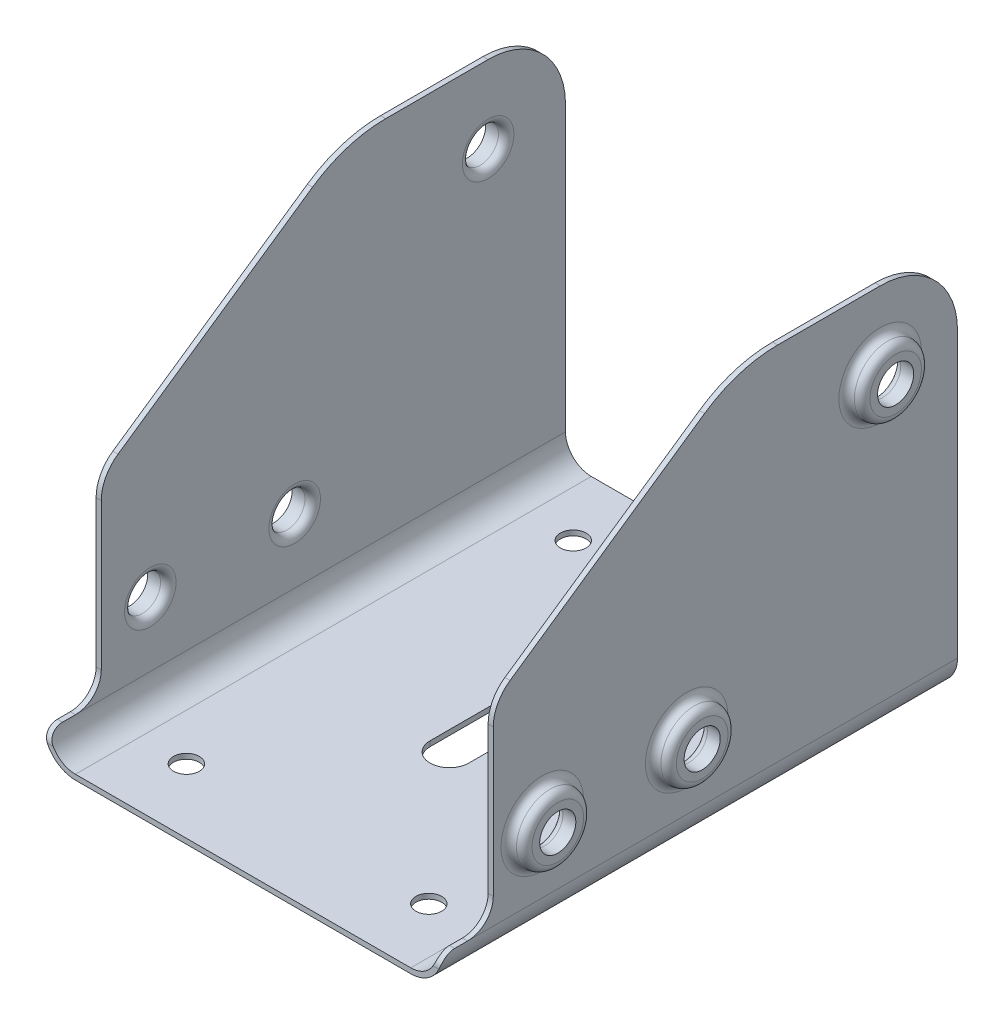
SolidWorks part; units mm, degrees
note: The reader was unsure of these and kept them because the rebuilt part matched: thickness of "Base-Flange1", "Edge-Flange1", "Sheet-Metal1", "Sheet-Metal2", "Sheet-Metal3", "Sheet-Metal4", "Sheet-Metal5", "Sheet-Metal6"; flange length of "Edge-Flange1".
ref_plane "Front Plane" through (0, 0, 0) normal (0, 0, 1) x (1, 0, 0)
ref_plane "Top Plane" through (0, 0, 0) normal (0, 1, 0) x (1, 0, 0)
ref_plane "Right Plane" through (0, 0, 0) normal (1, 0, 0) x (0, 0, -1)
sketch "Sketch1" plane through (0, 0, 0) normal (0, 1, 0) x (1, 0, 0)
  line L1 (-75, 100) -> (75, 100)
  line L2 (-75, 100) -> (-75, -100)
  line L3 (-75, -100) -> (75, -100)
  line L4 (75, 100) -> (75, -100)
  line L5 (-75, 100) -> (75, -100) construction
  line L6 (-75, -100) -> (75, 100) construction
  point P0 (0, 0)
  dimension "D1" = 200
  dimension "D2" = 150
base flange "Base-Flange1" sketch "Sketch1" thickness 2 reverse thickness direction no parameters "D1"=0.7366
edge flange "Edge-Flange1" sketch "Sketch13" flange profiles "Sketch13", "Sketch14" flange angle 90 flange length 150 flange position material outside bend radius 10 thickness 2 relief rectangular parameters "D6"=0, "D8"=1
sketch "Sketch13" plane through (75, 0, 0) normal (1, 0, 0) x (0, 0, -1)
  line L0 (-100, 0) -> (100, 0) construction
  line L1 (-100, 0) -> (100, 0)
  line L2 (-100, 0) -> (-100, 150)
  line L3 (-100, 150) -> (100, 150)
  line L4 (100, 150) -> (100, 0)
  dimension "D1" = 150
sketch "Sketch14" plane through (-75, 0, 0) normal (-1, 0, 0) x (0, 0, 1)
  line L0 (-100, 0) -> (100, 0) construction
  line L1 (-100, 0) -> (100, 0)
  line L2 (-100, 0) -> (-100, 150)
  line L3 (-100, 150) -> (100, 150)
  line L4 (100, 150) -> (100, 0)
  dimension "D1" = 150
bend "EdgeBend1" bend radius 10 bend angle 90 parameters "D5"=1
bend "EdgeBend2" bend radius 10 bend angle 90 parameters "D5"=2
sketch "Sketch15" plane through (-77, 0, 0) normal (-1, 0, 0) x (0, 0, 1)
  line L0 (-1.9165, 141.1807) -> (73.5072, 89.2432)
  line L1 (100, 150) -> (-100, 150) construction
  line L2 (-100, 99) -> (-100, 120)
  line L4 (90, 10) -> (95, 10)
  line L8 (-49, 150) -> (-30.274, 150)
  line L9 (-100, 99) -> (-100, -2)
  line L10 (-100, -2) -> (100, -2)
  line L11 (100, 71) -> (100, -2) construction
  line L12 (80, 76.889) -> (80, 20)
  line L13 (-70, 150) -> (-49, 150)
  line L14 (100, 5) -> (100, -2)
  arc A1 (-1.9165, 141.1807) -> (-30.274, 150) centre (-30.274, 100) ccw
  circle A2 centre (61, 35) radius 7
  circle A3 centre (-70, 120) radius 7
  circle A4 centre (5, 35) radius 7
  arc A5 (90, 10) -> (80, 20) centre (90, 20) cw
  arc A6 (80, 76.889) -> (73.5072, 89.2432) centre (65, 76.889) ccw
  arc A7 (100, 5) -> (95, 10) centre (95, 5) ccw
  arc A8 (-100, 120) -> (-70, 150) centre (-70, 120) cw
  point P18 (-14.7239, 150)
  point P27 (100, 10)
  point P34 (-100, 150)
  dimension "D5" = 50
  dimension "D6" = 95
  dimension "D7" = 39
  dimension "D8" = 37
  dimension "D9" = 37
  dimension "D10" = 14
  dimension "D11" = 14
  dimension "D12" = 30
  dimension "D13" = 30
  dimension "D15" = 10
  dimension "D4" = 15
  dimension "D17" = 5
  dimension "D18" = 30
  dimension "D2" = 145.448
  dimension "D3" = 101
  dimension "D14" = 20
  dimension "D16" = 91.5765
extrude "Cut-Extrude1" cut sketch "Sketch15" against normal through all flip side to cut
sketch "Sketch16" plane through (0, 0, 0) normal (0, 1, 0) x (1, 0, 0)
  line L0 (65, 100) -> (-65, 100) construction
  line L2 (0, 100) -> (0, -100) construction
  line L3 (-65, -100) -> (65, -100) construction
  line L4 (-77, 0) -> (75, 0) construction
  line L5 (-77, 30.274) -> (-77, 1.9165) construction
  line L6 (75, 30.274) -> (75, 1.9165) construction
  line L7 (0, 20) -> (0, -20) construction
  line L8 (7.5, 20) -> (7.5, -20)
  line L9 (-7.5, 20) -> (-7.5, -20)
  line L10 (-77, -90) -> (-77, 100) construction
  circle A2 centre (-47, 75) radius 5
  circle A5 centre (47, 75) radius 5
  circle A6 centre (47, -75) radius 5
  circle A7 centre (-47, -75) radius 5
  arc A8 (7.5, 20) -> (-7.5, 20) centre (0, 20) ccw
  arc A9 (-7.5, -20) -> (7.5, -20) centre (0, -20) ccw
  point P25 (0, 0)
  dimension "D1" = 10
  dimension "D2" = 25
  dimension "D3" = 30
  dimension "D4" = 15
  dimension "D5" = 40
extrude "Cut-Extrude2" cut sketch "Sketch16" against normal through all
sketch "Sketch17" plane through (-77, 0, 0) normal (-1, 0, 0) x (0, 0, 1)
  circle A0 centre (5, 35) radius 7
  circle A1 centre (5, 35) radius 7 construction
  circle A2 centre (5, 35) radius 13
  circle A3 centre (61, 35) radius 13
  circle A4 centre (61, 35) radius 7
  circle A5 centre (-70, 120) radius 7
  circle A6 centre (-70, 120) radius 7 construction
  circle A7 centre (-70, 120) radius 13
  dimension "D1" = 26
extrude "Boss-Extrude1" add sketch "Sketch17" along normal blind 6
mirror "Mirror1" about plane through (0, 0, 0) normal (1, 0, 0) of "Boss-Extrude1"
fillet "Fillet1" radius 3 18 edges at (-77, 48, 61) (-83, 22, 61) (-77, 48, 5) (-83, 22, 5) (-77, 133, -70) (-83, 107, -70) (77, 22, 61) (83, 22, 61) (77, 22, 5) (83, 22, 5) (77, 107, -70) (83, 107, -70) (75, 113, -70) (-75, 42, 5) (-75, 42, 61) (-75, 127, -70) (75, 28, 5) (75, 28, 61)
sketch "Bend-Lines1" [suppressed] plane through (0, 0, 0) normal (0, 1, 0) x (1, 0, 0)
sketch "Bounding-Box1" [suppressed] plane through (0, 0, 0) normal (0, 1, 0) x (1, 0, 0)
sheet metal parameters "Sheet-Metal1" thickness 2 parameters "D1"=0.7366
flat pattern "Flat-Pattern1" [suppressed]
sketch "Bend-Lines2" plane through (0, 0, 0) normal (0, 1, 0) x (1, 0, 0)
sketch "Bounding-Box2" [suppressed] plane through (0, 0, 0) normal (0, 1, 0) x (1, 0, 0)
sheet metal parameters "Sheet-Metal2" thickness 2 parameters "D1"=0.7366, "D7"=1
flat pattern "Flat-Pattern1" [suppressed]
sketch "Bend-Lines2" plane through (0, 0, 0) normal (0, 1, 0) x (1, 0, 0)
sketch "Bounding-Box2" [suppressed] plane through (0, 0, 0) normal (0, 1, 0) x (1, 0, 0)
bend of the flat pattern "Flatten-<EdgeBend1>1"
bend of the flat pattern "Flatten-<EdgeBend2>1"
sheet metal parameters "Sheet-Metal3" thickness 2 parameters "D1"=0.7366, "D7"=1
flat pattern "Flat-Pattern1"
sketch "Bend-Lines2" plane through (0, 0, 0) normal (0, 1, 0) x (1, 0, 0)
  line L0 (-75.2346, 100) -> (-75.2346, -100) construction
  line L1 (75.2346, -100) -> (75.2346, 100) construction
  line L2 (-75.2346, 100) -> (-75.2346, -100) construction
  line L3 (75.2346, -100) -> (75.2346, 100) construction
sketch3d "Bounding-Box2" [suppressed]
  line L0 (-225.4692, -100, 0) -> (225.4692, -100, 0) construction
  line L1 (-225.4692, 100, 0) -> (225.4692, 100, 0) construction
  line L2 (-225.4692, -100, 0) -> (-225.4692, 100, 0) construction
  line L3 (225.4692, -100, 0) -> (225.4692, 100, 0) construction
bend of the flat pattern "Flatten-<EdgeBend1>1"
bend of the flat pattern "Flatten-<EdgeBend2>1"
sheet metal parameters "Sheet-Metal4" thickness 2 parameters "D1"=0.7366, "D7"=1
flat pattern "Flat-Pattern1"
sketch "Bend-Lines2" plane through (0, 0, 0) normal (0, 1, 0) x (1, 0, 0)
  line L0 (-73.6394, -125) -> (-73.6394, 125) construction
  line L1 (73.6394, -125) -> (73.6394, 125) construction
  line L2 (-73.6394, -125) -> (-73.6394, 125) construction
  line L3 (73.6394, -125) -> (73.6394, 125) construction
sketch3d "Bounding-Box2" [suppressed]
  line L0 (-222.2788, -125, 0) -> (222.2788, -125, 0) construction
  line L1 (-222.2788, 125, 0) -> (222.2788, 125, 0) construction
  line L2 (-222.2788, -125, 0) -> (-222.2788, 125, 0) construction
  line L3 (222.2788, -125, 0) -> (222.2788, 125, 0) construction
bend of the flat pattern "Flatten-<EdgeBend1>1"
bend of the flat pattern "Flatten-<EdgeBend2>1"
sheet metal parameters "Sheet-Metal5" thickness 2 parameters "D1"=0.7366, "D7"=1
flat pattern "Flat-Pattern1"
sketch "Bend-Lines2" plane through (0, 0, 0) normal (0, 1, 0) x (1, 0, 0)
  line L0 (-73.6394, -125) -> (-73.6394, 125) construction
  line L1 (73.6394, -125) -> (73.6394, 125) construction
  line L2 (-73.6394, -125) -> (-73.6394, 125) construction
  line L3 (73.6394, -125) -> (73.6394, 125) construction
sketch3d "Bounding-Box2" [suppressed]
  line L0 (-222.2788, -125, 0) -> (222.2788, -125, 0) construction
  line L1 (-222.2788, 125, 0) -> (222.2788, 125, 0) construction
  line L2 (-222.2788, -125, 0) -> (-222.2788, 125, 0) construction
  line L3 (222.2788, -125, 0) -> (222.2788, 125, 0) construction
bend of the flat pattern "Flatten-<EdgeBend1>1"
bend of the flat pattern "Flatten-<EdgeBend2>1"
sheet metal parameters "Sheet-Metal6" thickness 2 parameters "D1"=0.7366, "D7"=1
flat pattern "Flat-Pattern1"
sketch "Bend-Lines2" plane through (0, 0, 0) normal (0, 1, 0) x (1, 0, 0)
  line L0 (-73.6394, -100) -> (-73.6394, 100) construction
  line L1 (73.6394, -100) -> (73.6394, 100) construction
  line L2 (-73.6394, -100) -> (-73.6394, 100) construction
  line L3 (73.6394, -100) -> (73.6394, 100) construction
sketch3d "Bounding-Box2" [suppressed]
  line L0 (-222.2788, -100, 0) -> (222.2788, -100, 0) construction
  line L1 (-222.2788, 100, 0) -> (222.2788, 100, 0) construction
  line L2 (-222.2788, -100, 0) -> (-222.2788, 100, 0) construction
  line L3 (222.2788, -100, 0) -> (222.2788, 100, 0) construction
bend of the flat pattern "Flatten-<EdgeBend1>1"
bend of the flat pattern "Flatten-<EdgeBend2>1"
